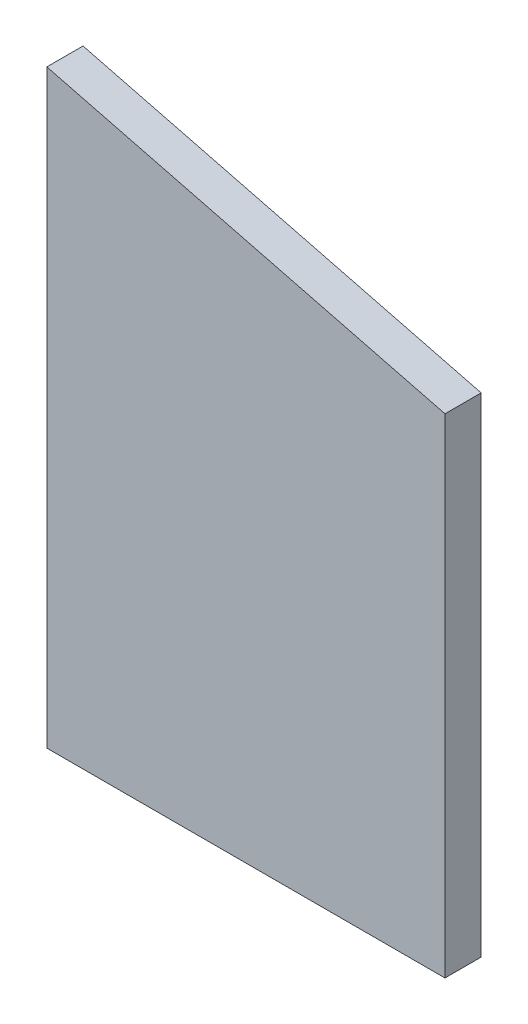
SolidWorks part; units mm, degrees
ref_plane "Plan de face" through (0, 0, 0) normal (0, 0, 1) x (1, 0, 0)
ref_plane "Plan de dessus" through (0, 0, 0) normal (0, 1, 0) x (1, 0, 0)
ref_plane "Plan de droite" through (0, 0, 0) normal (1, 0, 0) x (0, 0, -1)
sketch "Esquisse1" plane through (0, 0, 0) normal (0, 0, 1) x (1, 0, 0)
  line L0 (10, 173) -> (120, 145)
  line L1 (120, 145) -> (120, 10)
  line L2 (120, 10) -> (10, 10)
  line L3 (10, 10) -> (10, 173)
extrude "Boss.-Extru.1" add sketch "Esquisse1" against normal blind 10
